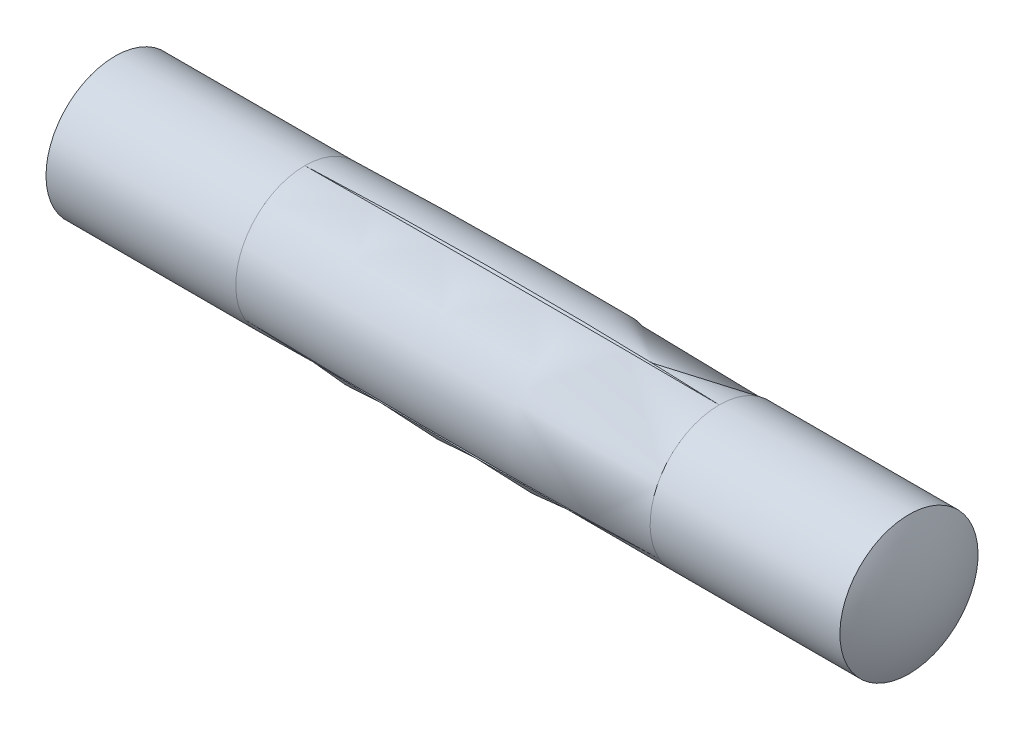
SolidWorks part; units mm, degrees
ref_plane "Plane1" through (0, 0, 0) normal (0, 0, 1) x (1, 0, 0)
ref_plane "Plane2" through (0, 0, 0) normal (0, 1, 0) x (1, 0, 0)
ref_plane "Plane3" through (0, 0, 0) normal (1, 0, 0) x (0, 0, -1)
sketch "Sketch1" plane through (0, 0, 0) normal (0, 0, 1) x (1, 0, 0)
  line L0 (-15, 0) -> (31.513, 0) construction
  line L1 (2.86, 0) -> (-2.86, 0) construction
  line L2 (-14.37, 2.5) -> (14.37, 2.5)
  line L3 (0, 19.94) -> (0, -13.9002) construction
  line L4 (0, -2.86) -> (0, 2.86) construction
  line L5 (-15, 0) -> (-15, -8.3947) construction
  line L6 (15, 0) -> (15, -8.3947) construction
  line L7 (-15, 0) -> (15, 0)
  arc A0 (-14.37, 2.5) -> (-15, 0) centre (-9.7247, 0) ccw
  arc A1 (14.37, 2.5) -> (15, 0) centre (9.7247, 0) cw
revolve "Revolve3" add sketch "Sketch1" angle 360 about L0
sketch "Sketch2" plane through (0, 0, 0) normal (0, 0, 1) x (1, 0, 0)
  line L0 (14.37, 2.5) -> (-14.37, 2.5) construction
  line L3 (0, 2.6) -> (6.8151, 2.6) construction
  line L4 (-7.5, 2.5) -> (-7.5, 0)
  line L5 (2.86, 0) -> (-2.86, 0) construction
  line L6 (-7.5, 0) -> (7.5, 0)
  line L7 (0, 2.6) -> (0, 0) construction
  line L8 (7.5, 2.5) -> (7.5, 0)
  line L9 (0, 0) -> (18.6878, 0) construction
  arc A0 (-7.5, 2.5) -> (7.5, 2.5) centre (0, -278.7) cw
revolve "Revolve4" add sketch "Sketch2" angle 360 about L9
sketch "Sketch3" plane through (0, 0, 0) normal (1, 0, 0) x (0, 0, -1)
  line L0 (0, 2.5) -> (-0.1147, 2.6638)
  line L1 (0, 2.9758) -> (0, -2.9758) construction
  line L2 (0, 2.5) -> (0, 2.9555) construction
  line L3 (0, 2.5) -> (0.1147, 2.6638)
  circle A0 centre (0, 0) radius 2.5 construction
  circle A1 centre (0, 0) radius 2.5 construction
  arc A2 (-0.1147, 2.6638) -> (0.1147, 2.6638) centre (0, 2.5) cw
  dimension "D1" = 0.2
  dimension "D2" = 70
extrude "Cut-Extrude1" cut sketch "Sketch3" against normal mid plane 15
pattern_circular "CirPattern2" count 3 over 360 about axis through (-15, 0, 0) along (1, 0, 0) of "Cut-Extrude1"
equation "\"D1@Sketch3\" = \"d2@Sketch2\" - \"d@Sketch1\""
equation "\"D1@Cut-Extrude1\" = \"l2@Sketch2\""
